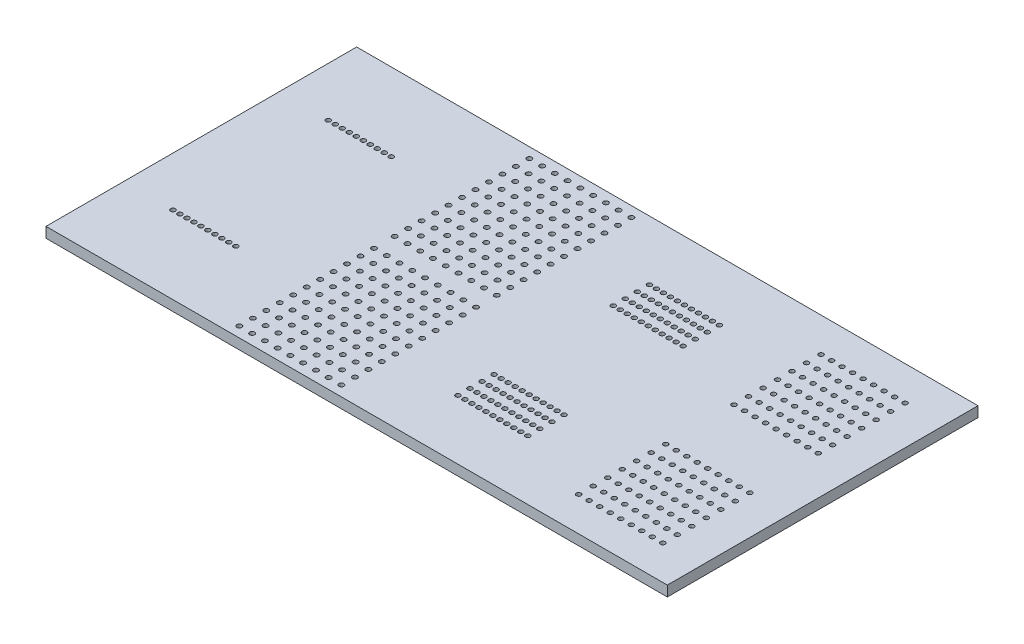
SolidWorks part; units mm, degrees
ref_plane "Plan de face" through (0, 0, 0) normal (0, 0, 1) x (1, 0, 0)
ref_plane "Plan de dessus" through (0, 0, 0) normal (0, 1, 0) x (1, 0, 0)
ref_plane "Plan de droite" through (0, 0, 0) normal (1, 0, 0) x (0, 0, -1)
sketch "Esquisse2" plane through (0, 0, 0) normal (0, 1, 0) x (1, 0, 0)
  line L1 (-60, -15) -> (60, -15)
  line L2 (-60, -15) -> (-60, 15)
  line L3 (-60, 15) -> (60, 15)
  line L4 (60, -15) -> (60, 15)
  line L5 (-60, -15) -> (60, 15) construction
  line L6 (-60, 15) -> (60, -15) construction
  point P0 (0, 0)
  dimension "D1" = 30
  dimension "D2" = 120
extrude "Boss.-Extru.1" add sketch "Esquisse2" along normal blind 2 contours L3 L4 L1 L2
sketch "Cavités" plane through (0, 0, 0) normal (0, 1, 0) x (1, 0, 0)
  line L0 (-60, -15) -> (60, -15) construction
  line L1 (-58.4, 15) -> (-30.4, 15) construction
  line L2 (-58.4, 15) -> (-58.4, -15) construction
  line L3 (-58.4, -15) -> (-30.4, -15) construction
  line L4 (-30.4, 15) -> (-30.4, -15) construction
  line L5 (-60, 15) -> (60, 15) construction
  line L6 (-28.8, 15) -> (-0.8, 15) construction
  line L7 (-28.8, 15) -> (-28.8, -15) construction
  line L8 (-28.8, -15) -> (-0.8, -15) construction
  line L9 (-0.8, 15) -> (-0.8, -15) construction
  line L10 (-30.4, 15) -> (-28.8, 15) construction
  line L11 (0.8, 15) -> (28.8, 15) construction
  line L12 (0.8, 15) -> (0.8, -15) construction
  line L13 (0.8, -15) -> (28.8, -15) construction
  line L14 (28.8, 15) -> (28.8, -15) construction
  line L15 (30.4, 15) -> (58.4, 15) construction
  line L16 (30.4, 15) -> (30.4, -15) construction
  line L17 (30.4, -15) -> (58.4, -15) construction
  line L18 (58.4, 15) -> (58.4, -15) construction
  line L19 (-0.8, 15) -> (0.8, 15) construction
  line L20 (28.8, 15) -> (30.4, 15) construction
  line L21 (-60, 15) -> (-58.4, 15) construction
  line L22 (58.4, 15) -> (60, 15) construction
  dimension "D1" = 28
  dimension "D2" = 1.6
sketch "Esquisse7" plane through (0, 2, 0) normal (0, 1, 0) x (1, 0, 0)
  line L0 (-58.4, 0) -> (-50.475, 0) construction
  line L5 (-58.4, 15) -> (-58.4, -15) construction
  line L6 (-38.325, 0) -> (-30.4, 0) construction
  line L7 (-30.4, 15) -> (-30.4, -15) construction
  line L8 (-50.475, 0) -> (-38.325, 0) construction
  dimension "D1" = 12.15
sketch "Esquisse8" plane through (0, 2, 0) normal (0, 1, 0) x (1, 0, 0)
  circle A0 centre (-50.475, 0) radius 0.45
  dimension "D1" = 0.9
extrude "Enlèv. mat.-Extru.3" cut sketch "Esquisse8" against normal up to next
pattern_linear "Répétition linéaire4" count 10 spacing 1.35 along (1, 0, 0) of "Enlèv. mat.-Extru.3"
sketch "Esquisse9" plane through (0, 2, 0) normal (0, 1, 0) x (1, 0, 0)
  line L0 (-28.8, 0) -> (-24.656, 0) construction
  line L1 (-24.656, 13) -> (-4.944, 13) construction
  line L2 (-24.656, 13) -> (-24.656, -13) construction
  line L3 (-24.656, -13) -> (-4.944, -13) construction
  line L4 (-4.944, 13) -> (-4.944, -13) construction
  line L5 (-28.8, 15) -> (-28.8, -15) construction
  line L6 (-4.944, 0) -> (-0.8, 0) construction
  line L7 (-0.8, 15) -> (-0.8, -15) construction
  dimension "D1" = 19.712
  dimension "D2" = 26
sketch "Esquisse10" plane through (0, 2, 0) normal (0, 1, 0) x (1, 0, 0)
  circle A0 centre (-24.656, 13) radius 0.475
  dimension "D1" = 0.95
extrude "Enlèv. mat.-Extru.4" cut sketch "Esquisse10" against normal up to next
pattern_linear "Répétition linéaire5" count 9 spacing 2.464 along (1, 0, 0) count 11 spacing 2.6 along (0, 0, 1) of "Enlèv. mat.-Extru.4"
sketch "Esquisse11" plane through (0, 2, 0) normal (0, 1, 0) x (1, 0, 0)
  line L0 (0.8, 0) -> (8.05, 0) construction
  line L1 (8.05, 3.4995) -> (21.55, 3.4995) construction
  line L2 (8.05, 3.4995) -> (8.05, -3.4995) construction
  line L3 (8.05, -3.4995) -> (21.55, -3.4995) construction
  line L4 (21.55, 3.4995) -> (21.55, -3.4995) construction
  line L5 (0.8, 15) -> (0.8, -15) construction
  line L6 (21.55, 0) -> (28.8, 0) construction
  line L7 (28.8, 15) -> (28.8, -15) construction
  dimension "D1" = 13.5
  dimension "D2" = 6.999
sketch "Esquisse12" plane through (0, 2, 0) normal (0, 1, 0) x (1, 0, 0)
  circle A0 centre (8.05, 3.4995) radius 0.45
  dimension "D1" = 0.9
extrude "Enlèv. mat.-Extru.5" cut sketch "Esquisse12" against normal up to next
pattern_linear "Répétition linéaire6" count 11 spacing 1.35 along (1, 0, 0) count 4 spacing 2.333 along (0, 0, 1) of "Enlèv. mat.-Extru.5"
sketch "Esquisse13" plane through (0, 2, 0) normal (0, 1, 0) x (1, 0, 0)
  line L0 (30.4, 0) -> (36.28, 0) construction
  line L1 (36.28, 8.4) -> (52.52, 8.4) construction
  line L2 (36.28, 8.4) -> (36.28, -8.4) construction
  line L3 (36.28, -8.4) -> (52.52, -8.4) construction
  line L4 (52.52, 8.4) -> (52.52, -8.4) construction
  line L5 (30.4, 15) -> (30.4, -15) construction
  line L6 (52.52, 0) -> (58.4, 0) construction
  line L7 (58.4, 15) -> (58.4, -15) construction
  dimension "D1" = 16.8
  dimension "D2" = 16.24
sketch "Esquisse14" plane through (0, 2, 0) normal (0, 1, 0) x (1, 0, 0)
  circle A0 centre (36.28, 8.4) radius 0.45
  dimension "D1" = 0.9
extrude "Enlèv. mat.-Extru.6" cut sketch "Esquisse14" against normal up to next
pattern_linear "Répétition linéaire7" count 9 spacing 2.03 along (1, 0, 0) count 7 spacing 2.8 along (0, 0, 1) of "Enlèv. mat.-Extru.6"
mirror "Symétrie1" about plane through (-60, 2, 15) normal (0, 0, -1) of bodies 114
